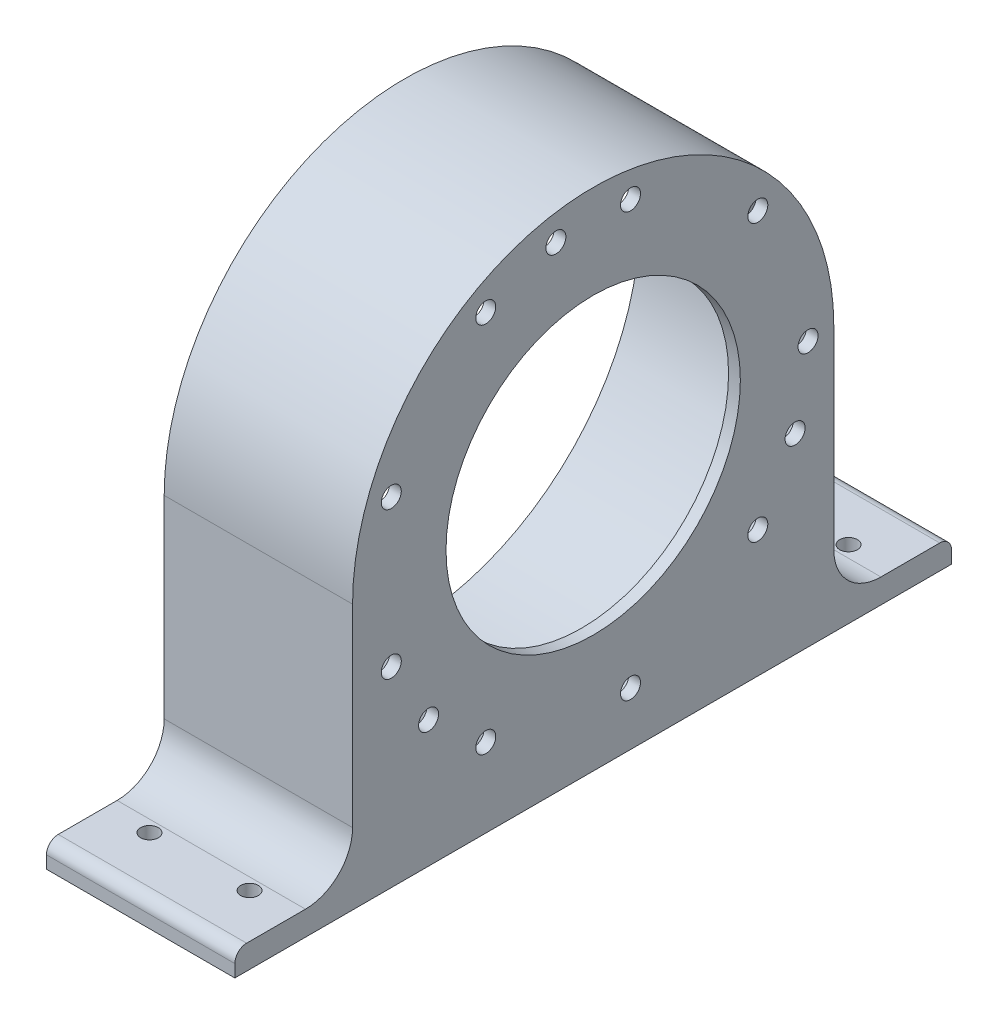
SolidWorks part; units mm, degrees
ref_plane "Front Plane" through (0, 0, 0) normal (0, 0, 1) x (1, 0, 0)
ref_plane "Top Plane" through (0, 0, 0) normal (0, 1, 0) x (1, 0, 0)
ref_plane "Right Plane" through (0, 0, 0) normal (1, 0, 0) x (0, 0, -1)
sketch "Sketch1" plane through (0, 0, 0) normal (1, 0, 0) x (0, 0, -1)
  line L0 (-45.3927, 0) -> (53.5456, 0) construction
  line L1 (0, 41.6536) -> (0, -48.2781) construction
  circle A0 centre (0, 0) radius 40.875
  circle A1 centre (0, 0) radius 25 construction
  circle A2 centre (0, 0) radius 5 construction
  circle A3 centre (-11.0978, 0) radius 2 construction
  dimension "D1" = 81.75
  dimension "D2" = 50
  dimension "D3" = 10
  dimension "D4" = 4
ref_plane "Plane1" through (0, 0, 0) normal (1, 0, 0) x (0, 0, -1)
sketch "Sketch4" plane through (0, 0, 0) normal (1, 0, 0) x (0, 0, -1)
  line L0 (-60.875, -45) -> (79.2008, -45) construction
  line L1 (-45.3927, 0) -> (53.5456, 0) construction
  line L2 (-60.875, -40.875) -> (60.875, -40.875) construction
  line L3 (-60.875, -40.875) -> (-60.875, -45)
  line L4 (-60.875, -45) -> (60.875, -45)
  line L5 (60.875, -40.875) -> (60.875, -45)
  line L6 (-45.3927, 0) -> (53.5456, 0) construction
  line L7 (0, 41.6536) -> (0, -48.2781) construction
  line L8 (0, 41.6536) -> (0, -48.2781) construction
  line L9 (0, -40.875) -> (78.6279, -40.875) construction
  line L10 (-40.875, 26.7143) -> (-40.875, -51.5044) construction
  line L11 (40.875, 26.7143) -> (40.875, -51.5044) construction
  line L12 (-60.875, -40.875) -> (-40.875, -40.875)
  line L13 (-40.875, 0) -> (-40.875, -40.875)
  line L14 (60.875, -40.875) -> (40.875, -40.875)
  line L15 (40.875, -40.875) -> (40.875, 0)
  circle A0 centre (0, 0) radius 40.875 construction
  circle A1 centre (0, 0) radius 40.875 construction
  arc A2 (-40.875, 0) -> (40.875, 0) centre (0, 0) cw
  point P19 (-60.875, -42.9375)
  dimension "D1" = 45
  dimension "D2" = 20
  dimension "D3" = 20
extrude "Boss-Extrude2" add sketch "Sketch4" against normal blind 32
sketch "Sketch2" plane through (0, 0, 0) normal (1, 0, 0) x (0, 0, -1)
  line L0 (0, 41.6536) -> (0, -48.2781) construction
  line L1 (0, 41.6536) -> (0, -48.2781) construction
  line L2 (-45.3927, 0) -> (53.5456, 0) construction
  line L3 (-45.3927, 0) -> (53.5456, 0) construction
  circle A0 centre (0, 0) radius 25 construction
  circle A1 centre (0, 0) radius 25
extrude "Cut-Extrude1" cut sketch "Sketch2" against normal blind 40 and the other way blind 10
sketch "Sketch3" plane through (0, 0, 0) normal (1, 0, 0) x (0, 0, -1)
  circle A0 centre (0, 0) radius 39.875
  dimension "D1" = 79.75
extrude "Cut-Extrude2" cut sketch "Sketch3" against normal blind 40 from offset 2 offset against normal yes
fillet "Fillet1" radius 8 2 edges at (-16, -40.875, 40.875) (-16, -40.875, -40.875)
fillet "Fillet2" radius 2 2 edges at (-16, -40.875, -60.875) (-16, -40.875, 60.875)
sketch "Sketch5" plane through (0, 0, 0) normal (1, 0, 0) x (0, 0, -1)
  line L0 (0, 41.6536) -> (0, -48.2781) construction
  line L1 (0, 41.6536) -> (0, -48.2781) construction
  line L2 (-45.3927, 0) -> (53.5456, 0) construction
  line L3 (-45.3927, 0) -> (53.5456, 0) construction
  line L4 (-27.9606, -23.4617) -> (34.2988, -12.4837) construction
  line L5 (-18.25, -31.6099) -> (27.9606, -23.4617) construction
  circle A12 centre (0, 0) radius 36.5 construction
  circle A13 centre (36.5, 0) radius 1.7
  circle A14 centre (27.9606, -23.4617) radius 1.7
  circle A15 centre (6.3382, -35.9455) radius 1.7
  circle A16 centre (-18.25, -31.6099) radius 1.7
  circle A17 centre (-34.2988, -12.4837) radius 1.7
  circle A18 centre (-34.2988, 12.4837) radius 1.7
  circle A19 centre (-18.25, 31.6099) radius 1.7
  circle A20 centre (6.3382, 35.9455) radius 1.7
  circle A21 centre (27.9606, 23.4617) radius 1.7
  circle A22 centre (34.2988, -12.4837) radius 1.7
  circle A23 centre (-27.9606, -23.4617) radius 1.7
  circle A24 centre (-6.3382, 35.9455) radius 1.7
  point P14 (0.0024, 0.9575)
  point P29 (0, 0)
  point P33 (-0.2001, -0.9798)
  point P37 (0, 0)
  dimension "D1" = 3.4
  dimension "D4" = 3
  dimension "D7" = 73
  dimension "D2" = 9
  dimension "D3" = 3.4
extrude "Cut-Extrude3" cut sketch "Sketch5" against normal blind 10 and the other way blind 10
ref_plane "Plane2" through (0, -45, 0) normal (0, -1, 0) x (-1, 0, 0)
sketch "Sketch6" plane through (0, -45, 0) normal (0, -1, 0) x (-1, 0, 0)
  line L0 (60.0956, 0) -> (-21.0706, 0) construction
  line L1 (16, -60.875) -> (16, 63.4495) construction
  line L2 (32, -60.875) -> (0, -60.875) construction
  line L3 (-22.2054, 50.875) -> (53.665, 50.875) construction
  line L4 (32, 60.875) -> (0, 60.875) construction
  line L5 (32, 60.875) -> (0, 60.875) construction
  line L6 (-22.2054, -50.875) -> (53.665, -50.875) construction
  line L7 (0, -60.875) -> (0, 60.875) construction
  line L8 (0, -60.875) -> (0, 60.875) construction
  circle A1 centre (7.5, 50.875) radius 1.5
  circle A2 centre (24.5, 50.875) radius 1.5
  circle A3 centre (24.5, -50.875) radius 1.5
  circle A4 centre (7.5, -50.875) radius 1.5
  dimension "D1" = 10
  dimension "D2" = 3
  dimension "D3" = 7.5
extrude "Cut-Extrude4" cut sketch "Sketch6" against normal blind 7 and the other way blind 5
